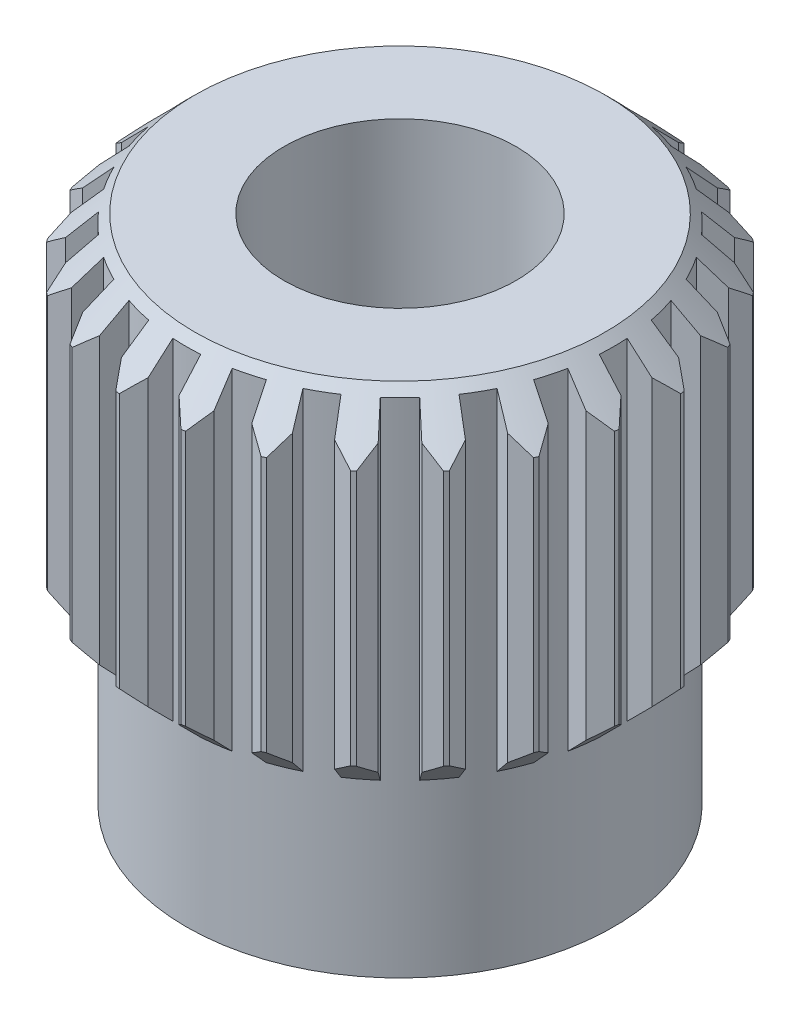
SolidWorks part; units mm, degrees
material "Brass"
ref_plane "Front Plane" through (0, 0, 0) normal (0, 0, 1) x (1, 0, 0)
ref_plane "Top Plane" through (0, 0, 0) normal (0, 1, 0) x (1, 0, 0)
ref_plane "Right Plane" through (0, 0, 0) normal (1, 0, 0) x (0, 0, -1)
sketch "Sketch1" plane through (0, 0, 0) normal (0, 1, 0) x (1, 0, 0)
  circle A0 centre (0, 0) radius 5.42
  circle A1 centre (0, 0) radius 2.5
  dimension "D1" = 10.84
  dimension "D2" = 5
extrude "Boss-Extrude1" add sketch "Sketch1" along normal blind 11
sketch "Sketch2" plane through (0, 0, 0) normal (0, -1, 0) x (1, 0, 0)
  circle A0 centre (0, 0) radius 4.6
  dimension "D1" = 9.2
extrude "Cut-Extrude1" cut sketch "Sketch2" against normal blind 3.5 flip side to cut
chamfer "Chamfer2" distance 1 angle 45 2 edges at (0, 11, 5.42) (0, 3.5, -5.42)
ref_axis "Axis1" through (0, 11.55, 0) along (0, -1, 0)
sketch "Sketch3" plane through (0, 0, 0) normal (0, 1, 0) x (1, 0, 0)
  line L0 (-0.3, -4.5902) -> (-0.3326, -5.0891)
  line L1 (-0.5, -7.6503) -> (0.5, -7.6503)
  line L2 (0.5, -7.6503) -> (0.3632, -5.5565)
  line L3 (0, 0) -> (0, -7.6503) construction
  line L4 (0.3326, -5.0891) -> (0.8653, -5.5565)
  line L5 (0.8653, -5.5565) -> (0.3632, -5.5565)
  line L6 (-0.8653, -5.5565) -> (-0.3326, -5.0891)
  line L7 (-0.3632, -5.5565) -> (-0.5, -7.6503)
  line L8 (0.3326, -5.0891) -> (0.3, -4.5902)
  line L9 (-0.3632, -5.5565) -> (-0.8653, -5.5565)
  circle A0 centre (0, 0) radius 4.6 construction
  arc A1 (-0.3, -4.5902) -> (0.3, -4.5902) centre (0, 0) ccw
  dimension "D1" = 1
  dimension "D2" = 0.6
  dimension "D3" = 45
  dimension "D4" = 45
  dimension "D5" = 0.5
extrude "Cut-Extrude2" cut sketch "Sketch3" along normal through all
pattern_circular "CirPattern1" count 24 every 15 about axis through (0, 11.55, 0) along (0, -1, 0) of "Cut-Extrude2"
